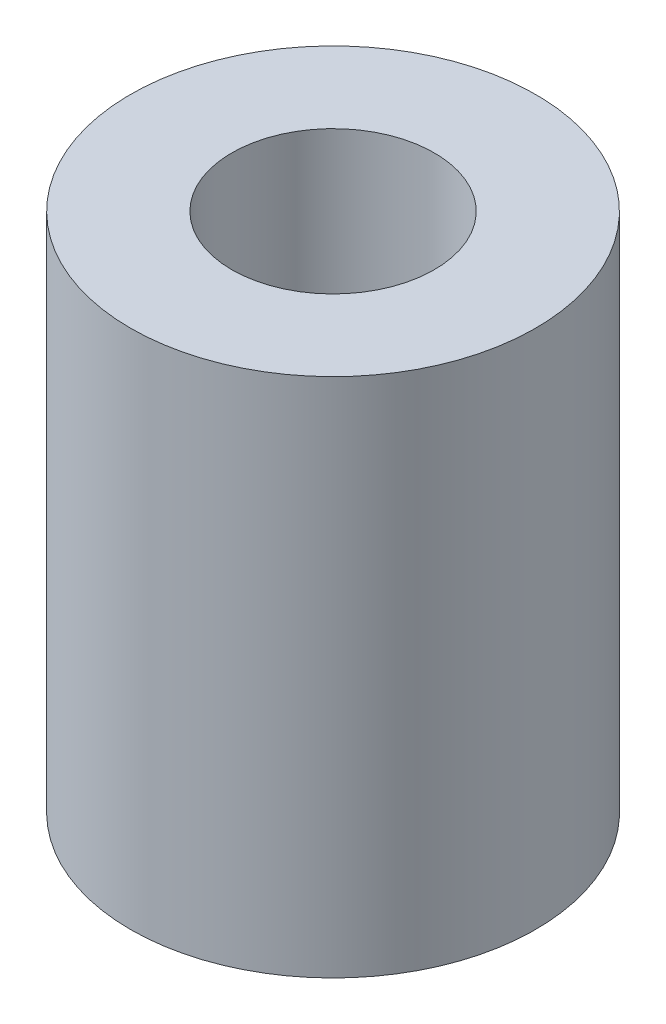
SolidWorks part; units mm, degrees
material "Настроенная пользователем пластмасса"
ref_plane "Front" through (0, 0, 0) normal (0, 0, 1) x (1, 0, 0)
ref_plane "Top" through (0, 0, 0) normal (0, 1, 0) x (1, 0, 0)
ref_plane "Right" through (0, 0, 0) normal (1, 0, 0) x (0, 0, -1)
sketch "Эскиз1" plane through (0, 0, 0) normal (0, 1, 0) x (1, 0, 0)
  circle A0 centre (0, 0) radius 3.5
  circle A1 centre (0, 0) radius 1.75
  dimension "D1" = 7
  dimension "D2" = 3.5
extrude "Бобышка-Вытянуть1" add sketch "Эскиз1" along normal blind 9
